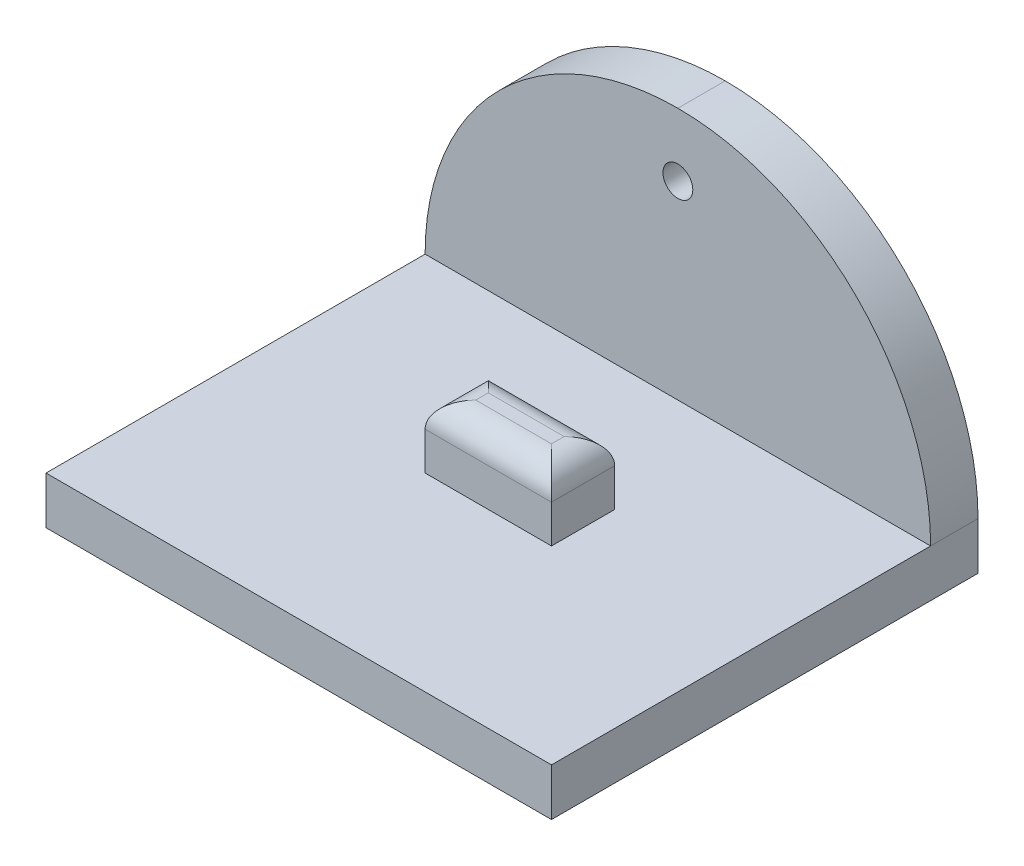
SolidWorks part; units mm, degrees
ref_plane "Front Plane" through (0, 0, 0) normal (0, 0, 1) x (1, 0, 0)
ref_plane "Top Plane" through (0, 0, 0) normal (0, 1, 0) x (1, 0, 0)
ref_plane "Right Plane" through (0, 0, 0) normal (1, 0, 0) x (0, 0, -1)
sketch "Sketch1" plane through (0, 0, 0) normal (1, 0, 0) x (0, 0, -1)
  line L0 (0, 0) -> (-42.8625, 0)
  line L1 (-42.8625, 0) -> (-42.8625, 4.7625)
  line L2 (-42.8625, 4.7625) -> (-4.7625, 4.7625)
  line L3 (-4.7625, 4.7625) -> (-4.7625, 30.1625)
  line L4 (-4.7625, 30.1625) -> (0, 30.1625)
  line L5 (0, 30.1625) -> (0, 0)
  dimension "D1" = 38.1
  dimension "D2" = 25.4
  dimension "D3" = 4.7625
extrude "Boss-Extrude1" add sketch "Sketch1" along normal blind 50.8
sketch "Sketch2" plane through (0, 4.7625, 0) normal (0, 1, 0) x (1, 0, 0)
  line L0 (50.8, -42.8625) -> (0, -42.8625) construction
  line L1 (19.05, -23.8125) -> (31.75, -23.8125)
  line L2 (19.05, -23.8125) -> (19.05, -17.4625)
  line L3 (19.05, -17.4625) -> (31.75, -17.4625)
  line L4 (31.75, -23.8125) -> (31.75, -17.4625)
  line L7 (50.8, -4.7625) -> (0, -4.7625) construction
  point P4 (25.4, -23.8125)
  point P7 (25.4, -42.8625)
  dimension "D1" = 6.35
  dimension "D2" = 12.7
  dimension "D3" = 12.7
extrude "Boss-Extrude2" add sketch "Sketch2" along normal blind 6.35
sketch "Sketch3" plane through (0, 0, 4.7625) normal (0, 0, 1) x (1, 0, 0)
  line L0 (50.8, 30.1625) -> (0, 30.1625) construction
  line L1 (50.8, 4.7625) -> (0, 4.7625) construction
  circle A0 centre (25.4, 23.8125) radius 1.5
  point P5 (25.4, 30.1625)
  dimension "D1" = 3
  dimension "D2" = 19.05
extrude "Cut-Extrude1" cut sketch "Sketch3" against normal through all
fillet "Fillet1" radius 2.54 4 edges at (25.4, 11.1125, 17.4625) (31.75, 11.1125, 20.6375) (25.4, 11.1125, 23.8125) (19.05, 11.1125, 20.6375)
fillet "Fillet2" radius 25.4 2 edges at (50.8, 30.1625, 2.3813) (0, 30.1625, 2.3813)
